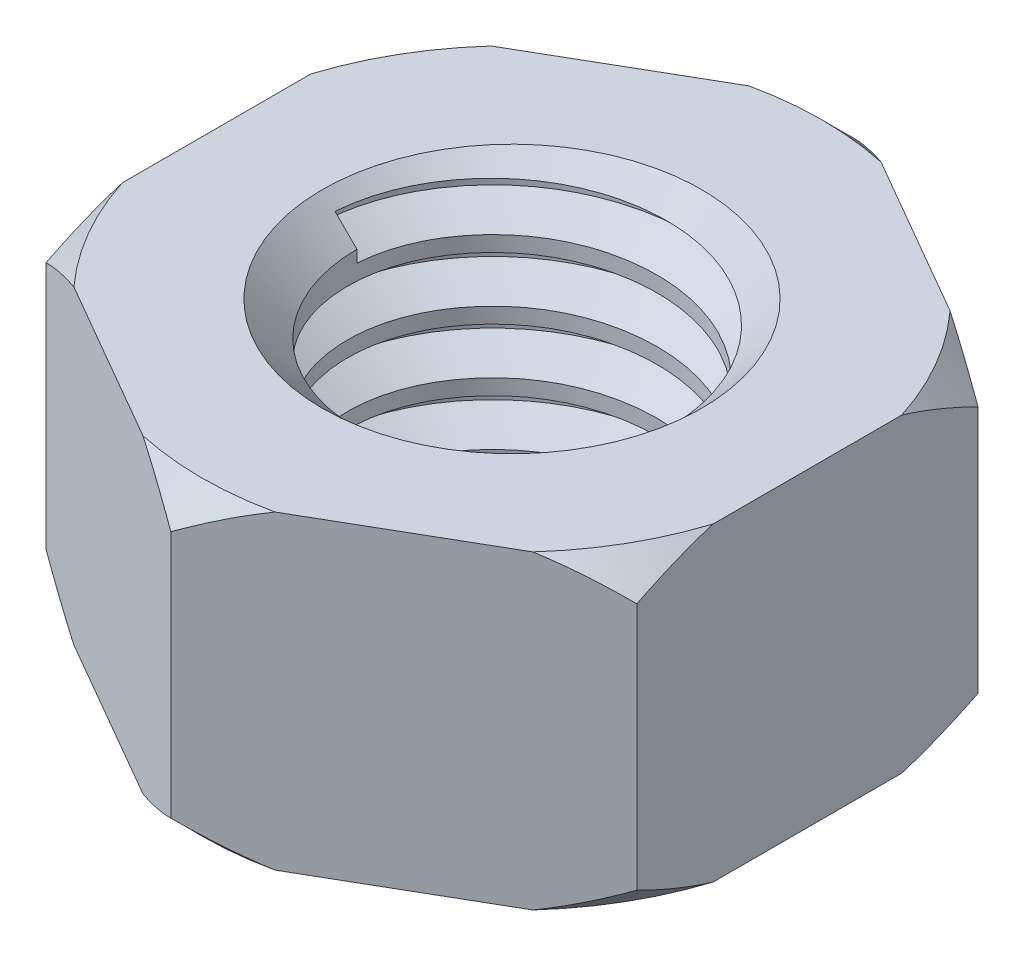
SolidWorks part; units mm, degrees
ref_plane "Front Plane" through (0, 0, 0) normal (0, 0, 1) x (1, 0, 0)
ref_plane "Top Plane" through (0, 0, 0) normal (0, 1, 0) x (1, 0, 0)
ref_plane "Right Plane" through (0, 0, 0) normal (1, 0, 0) x (0, 0, -1)
sketch "Sketch2" plane through (0, 0, 0) normal (0, 1, 0) x (1, 0, 0)
  line L13 (0, -55) -> (0, 55) construction
  line L14 (0, 5.5) -> (-4.7631, 2.75)
  line L15 (-4.7631, 2.75) -> (-4.7631, -2.75)
  line L16 (-4.7631, -2.75) -> (0, -5.5)
  line L17 (0, -5.5) -> (4.7631, -2.75)
  line L18 (4.7631, -2.75) -> (4.7631, 2.75)
  line L19 (4.7631, 2.75) -> (0, 5.5)
  circle A0 centre (0, 0) radius 4.7631 construction
  dimension "D1" = 4.7631
extrude "Boss-Extrude1" add sketch "Sketch2" along normal blind 5
sketch "Sketch3" plane through (0, 0, 0) normal (1, 0, 0) x (0, 0, -1)
  line L1 (5.5, 5) -> (2.75, 5) construction
  line L3 (5.5, 5) -> (5.5, 0) construction
  line L4 (5.5, 4.5) -> (5, 5)
  line L5 (5.5, 2.5) -> (-5.8997, 2.5) construction
  line L7 (5.5, 0.5) -> (5, 0)
  line L9 (0, 6.5514) -> (0, -1.8336) construction
  arc A0 (5, 5) -> (5.5, 4.5) centre (5.25, 4.75) cw
  arc A1 (5.5, 0.5) -> (5, 0) centre (5.25, 0.25) cw
revolve "Cut-Revolve2" cut sketch "Sketch3" angle 360 about L9
sketch "Sketch5" plane through (0, 5, 0) normal (0, 1, 0) x (1, 0, 0)
  circle A0 centre (0, 0) radius 2.5
  dimension "D1" = 5
extrude "Cut-Extrude1" cut sketch "Sketch5" against normal through all
thread "Thread1" pitch 1 method cut profile "Thread Profile1" start angle 0, offset 0, length 13, pitch 1, diameter 5
ref_plane "Plane1" through (-2.5, 5, 0) normal (0, 0, 1) x (-1, 0, 0)
sketch "Thread Profile1" plane through (-2.5, 5, 0) normal (0, 0, 1) x (-1, 0, 0)
  line L0 (0, 0) -> (0, 1) construction
  line L1 (0, 0) -> (0.5413, 0.3125)
  line L2 (0.5413, 0.3125) -> (0.5413, 0.4375)
  line L3 (0.5413, 0.4375) -> (0, 0.75)
  line L4 (0.5413, 0.375) -> (0, 0.375) construction
  line L11 (0, 0) -> (0, 0.75)
  point P2 (0, 0)
  dimension "Pitch" = 1
  dimension "Profile_Angle" = 60
  dimension "Profile_Land" = 0.125
  dimension "Profile_Height" = 0.5413
sketch "Sketch10" plane through (0, 0, 0) normal (1, 0, 0) x (0, 0, -1)
  line L0 (-2.3599, 5.4476) -> (-2.3599, 4.3033)
  line L1 (-2.3599, 4.3033) -> (-3.5933, 5.5367)
  line L2 (-3.5933, 5.5367) -> (-2.3599, 5.4476)
  line L3 (0, 6.459) -> (0, -2.0728) construction
  line L4 (5.5, 2.5) -> (-5.5, 2.5) construction
  line L5 (5.5, 4.5) -> (5.5, 0.5) construction
  line L6 (-5.5, 4.5) -> (-5.5, 0.5) construction
  line L7 (-3.5933, -0.5367) -> (-2.3599, -0.4476)
  line L8 (-2.3599, 0.6967) -> (-3.5933, -0.5367)
  line L9 (-2.3599, -0.4476) -> (-2.3599, 0.6967)
  spline S0 degree 2 poles (0, 5) (1.0355, 4.9375) (1.7678, 4.875) (2.5, 4.8125) (2.5, 4.75) (2.5, 4.6875) (1.7678, 4.625) (1.0355, 4.5625) (0, 4.5) (-1.0355, 4.4375) (-1.7678, 4.375) (-2.5, 4.3125) (-2.5, 4.25) (-2.5, 4.1875) (-1.7678, 4.125) (-1.0355, 4.0625) (0, 4) (1.0355, 3.9375) (1.7678, 3.875) (2.5, 3.8125) (2.5, 3.75) (2.5, 3.6875) (1.7678, 3.625) (1.0355, 3.5625) (0, 3.5) (-1.0355, 3.4375) (-1.7678, 3.375) (-2.5, 3.3125) (-2.5, 3.25) (-2.5, 3.1875) (-1.7678, 3.125) (-1.0355, 3.0625) (0, 3) (1.0355, 2.9375) (1.7678, 2.875) (2.5, 2.8125) (2.5, 2.75) (2.5, 2.6875) (1.7678, 2.625) (1.0355, 2.5625) (0, 2.5) (-1.0355, 2.4375) (-1.7678, 2.375) (-2.5, 2.3125) (-2.5, 2.25) (-2.5, 2.1875) (-1.7678, 2.125) (-1.0355, 2.0625) (0, 2) (1.0355, 1.9375) (1.7678, 1.875) (2.5, 1.8125) (2.5, 1.75) (2.5, 1.6875) (1.7678, 1.625) (1.0355, 1.5625) (0, 1.5) (-1.0355, 1.4375) (-1.7678, 1.375) (-2.5, 1.3125) (-2.5, 1.25) (-2.5, 1.1875) (-1.7678, 1.125) (-1.0355, 1.0625) (0, 1) (1.0355, 0.9375) (1.7678, 0.875) (2.5, 0.8125) (2.5, 0.75) (2.5, 0.6875) (1.7678, 0.625) (1.0355, 0.5625) (0, 0.5) (-1.0355, 0.4375) (-1.7678, 0.375) (-2.5, 0.3125) (-2.5, 0.25) (-2.5, 0.1875) (-1.7678, 0.125) (-1.0355, 0.0625) (0, 0) knots 0 0 0 0.009615 0.009615 0.019231 0.019231 0.028846 0.028846 0.038462 0.038462 0.048077 0.048077 0.057692 0.057692 0.067308 0.067308 0.076923 0.076923 0.086538 0.086538 0.096154 0.096154 0.105769 0.105769 0.115385 0.115385 0.125 0.125 0.134615 0.134615 0.144231 0.144231 0.153846 0.153846 0.163462 0.163462 0.173077 0.173077 0.182692 0.182692 0.192308 0.192308 0.201923 0.201923 0.211538 0.211538 0.221154 0.221154 0.230769 0.230769 0.240385 0.240385 0.25 0.25 0.259615 0.259615 0.269231 0.269231 0.278846 0.278846 0.288462 0.288462 0.298077 0.298077 0.307692 0.307692 0.317308 0.317308 0.326923 0.326923 0.336538 0.336538 0.346154 0.346154 0.355769 0.355769 0.365385 0.365385 0.375 0.375 0.384615 0.384615 0.384615 weights 1 0.92388 1 0.92388 1 0.92388 1 0.92388 1 0.92388 1 0.92388 1 0.92388 1 0.92388 1 0.92388 1 0.92388 1 0.92388 1 0.92388 1 0.92388 1 0.92388 1 0.92388 1 0.92388 1 0.92388 1 0.92388 1 0.92388 1 0.92388 1 0.92388 1 0.92388 1 0.92388 1 0.92388 1 0.92388 1 0.92388 1 0.92388 1 0.92388 1 0.92388 1 0.92388 1 0.92388 1 0.92388 1 0.92388 1 0.92388 1 0.92388 1 0.92388 1 0.92388 1 0.92388 1 0.92388 1 0.92388 1 construction
revolve "Cut-Revolve3" cut sketch "Sketch10" angle 360 about L3
